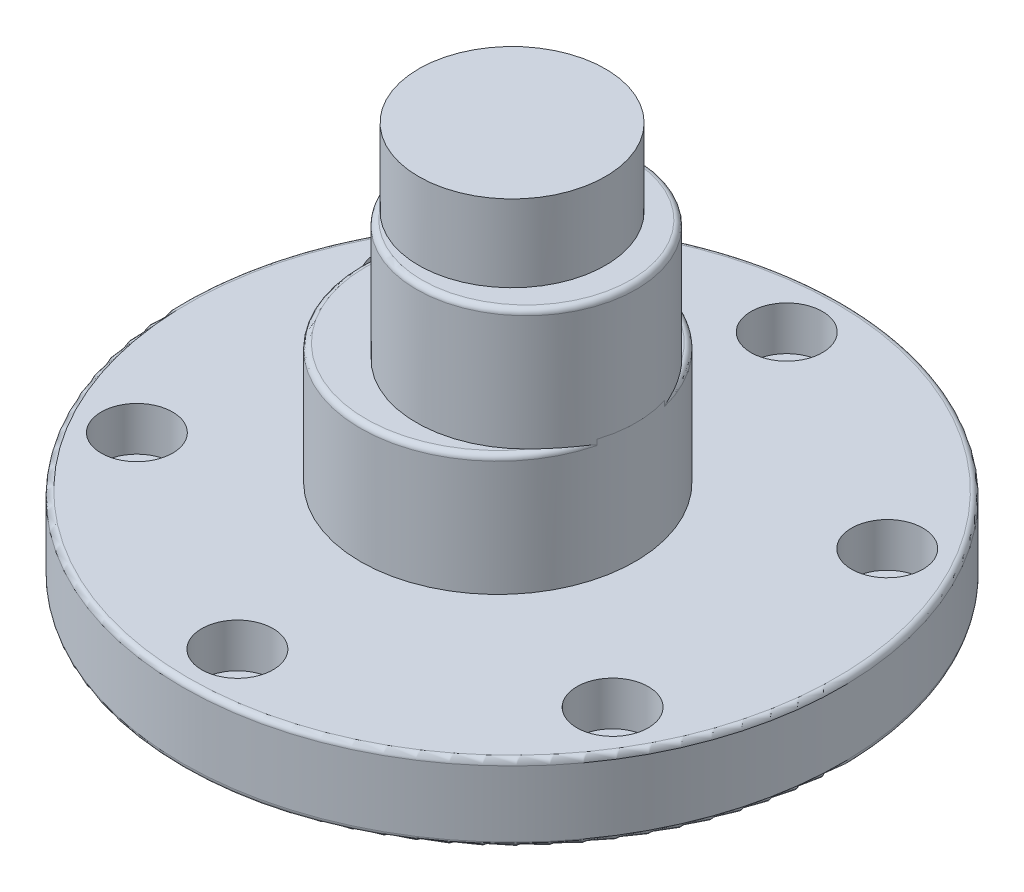
SolidWorks part; units mm, degrees
ref_plane "Front Plane" through (0, 0, 0) normal (0, 0, 1) x (1, 0, 0)
ref_plane "Top Plane" through (0, 0, 0) normal (0, 1, 0) x (1, 0, 0)
ref_plane "Right Plane" through (0, 0, 0) normal (1, 0, 0) x (0, 0, -1)
sketch "Sketch1" plane through (0, 0, 0) normal (0, 1, 0) x (1, 0, 0)
  circle A0 centre (0, 0) radius 25 construction
  circle A1 centre (0, 0) radius 30
  circle A2 centre (0, 25) radius 2.05
  circle A3 centre (21.6506, 12.5) radius 2.05
  circle A4 centre (21.6506, -12.5) radius 2.05
  circle A5 centre (0, -25) radius 2.05
  circle A6 centre (-21.6506, -12.5) radius 2.05
  circle A7 centre (-21.6506, 12.5) radius 2.05
  point P18 (0, 0)
  dimension "D1" = 50
  dimension "D2" = 60
  dimension "D3" = 4.1
  dimension "D4" = 6
extrude "Boss-Extrude1" add sketch "Sketch1" along normal blind 7
sketch "Sketch2" plane through (0, 7, 0) normal (0, 1, 0) x (1, 0, 0)
  circle A0 centre (-1.3, 0) radius 12.5
  point P0 (0, 0)
  point P1 (-1.3, 0)
  dimension "D2" = 25
  dimension "D1" = 1.3
extrude "Boss-Extrude2" add sketch "Sketch2" along normal blind 11
sketch "Sketch3" plane through (0, 18, 0) normal (0, 1, 0) x (1, 0, 0)
  circle A0 centre (1.3, 0) radius 10
  point P0 (1.3, 0)
  dimension "D2" = 20
  dimension "D1" = 1.3
extrude "Boss-Extrude3" add sketch "Sketch3" along normal blind 11
fillet "Fillet1" radius 0.5 4 edges at (1.3, 29, 10) (-13.8, 18, 0) (0, 0, 30) (0, 7, 30)
sketch "Sketch4" plane through (0, 7, 0) normal (0, 1, 0) x (1, 0, 0)
  circle A0 centre (0, 25) radius 3.25
  circle A1 centre (21.6506, 12.5) radius 3.25
  circle A2 centre (21.6506, -12.5) radius 3.25
  circle A3 centre (0, -25) radius 3.25
  circle A4 centre (-21.6506, -12.5) radius 3.25
  circle A5 centre (-21.6506, 12.5) radius 3.25
  point P16 (0, 0)
  dimension "D1" = 6.5
  dimension "D2" = 6
extrude "Cut-Extrude1" cut sketch "Sketch4" against normal blind 4
sketch "Sketch5" plane through (0, 29, 0) normal (0, 1, 0) x (1, 0, 0)
  circle A0 centre (0, 0) radius 8.5
  dimension "D1" = 17
extrude "Boss-Extrude4" add sketch "Sketch5" along normal blind 7
